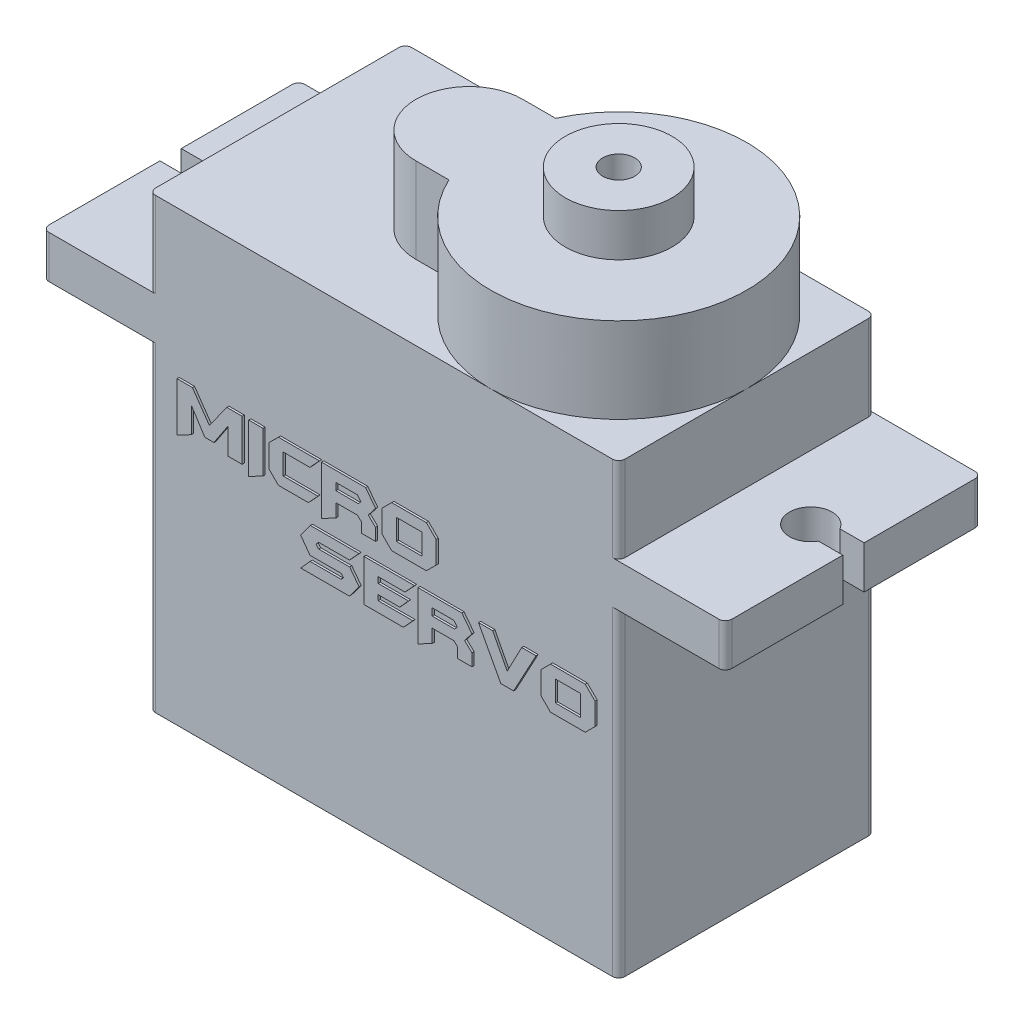
SolidWorks part; units mm, degrees
material "Acrilico TEC"
ref_plane "Front Plane" through (0, 0, 0) normal (0, 0, 1) x (1, 0, 0)
ref_plane "Top Plane" through (0, 0, 0) normal (0, 1, 0) x (1, 0, 0)
ref_plane "Right Plane" through (0, 0, 0) normal (1, 0, 0) x (0, 0, -1)
sketch "Sketch1" plane through (0, 0, 0) normal (0, 1, 0) x (1, 0, 0)
  line L1 (-16, -6) -> (16, -6)
  line L2 (-16, -6) -> (-16, 6)
  line L3 (-16, 6) -> (16, 6)
  line L4 (16, -6) -> (16, 6)
  line L5 (-16, -6) -> (16, 6) construction
  line L6 (-16, 6) -> (16, -6) construction
  point P0 (0, 0)
  dimension "D1" = 32
  dimension "D2" = 12
extrude "Boss-Extrude1" add sketch "Sketch1" along normal blind 2
sketch "Sketch2" plane through (0, 0, 0) normal (0, -1, 0) x (1, 0, 0)
  line L0 (-16, 6) -> (16, 6) construction
  line L1 (-11, -6) -> (11, -6)
  line L2 (-11, -6) -> (-11, 6)
  line L3 (-11, 6) -> (11, 6)
  line L4 (11, -6) -> (11, 6)
  line L5 (-11, -6) -> (11, 6) construction
  line L6 (-11, 6) -> (11, -6) construction
  point P0 (0, 0)
  dimension "D1" = 22
extrude "Boss-Extrude2" add sketch "Sketch2" along normal blind 15
sketch "Sketch3" plane through (0, 2, 0) normal (0, 1, 0) x (1, 0, 0)
  line L0 (16, 6) -> (-16, 6) construction
  line L1 (-11, -6) -> (11, -6)
  line L2 (-11, -6) -> (-11, 6)
  line L3 (-11, 6) -> (11, 6)
  line L4 (11, -6) -> (11, 6)
  line L5 (-11, -6) -> (11, 6) construction
  line L6 (-11, 6) -> (11, -6) construction
  point P0 (0, 0)
  dimension "D1" = 22
extrude "Boss-Extrude3" add sketch "Sketch3" along normal blind 4
sketch "Sketch4" plane through (0, 6, 0) normal (0, 1, 0) x (1, 0, 0)
  line L0 (11, 6) -> (-1, 6)
  line L1 (11, 6) -> (-11, 6) construction
  line L2 (-1, 6) -> (-1, -6)
  line L3 (-11, -6) -> (11, -6) construction
  line L4 (-1, -6) -> (11, 6)
  circle A0 centre (5, 0) radius 6
  dimension "D1" = 12
extrude "Boss-Extrude4" add sketch "Sketch4" along normal blind 4 contours L4 A0 | A0 L4 region at (3.1994, 6, -1.8006) region at (6.8006, 6, 1.8006)
sketch "Sketch5" plane through (0, 6, 0) normal (0, 1, 0) x (1, 0, 0)
  line L0 (5, 0) -> (-2, 0)
  line L1 (-2, 2.5) -> (-0.4544, 2.5)
  line L2 (-2, -2.5) -> (-0.4544, -2.5)
  circle A0 centre (-2, 0) radius 2.5
  circle A1 centre (5, 0) radius 6 construction
  circle A2 centre (5, 0) radius 6
  arc M1 (5, -6) -> (5, 6) centre (5, 0) cw
  dimension "D2" = 5
  dimension "D1" = 7
extrude "Boss-Extrude5" add sketch "Sketch5" along normal blind 4 contours A0 L1 M1 | A0 L2 M1 | A0 M1 region at (-2.4814, 6, 0) region at (-0.901, 6, -2.3763) region at (-0.901, 6, 2.3763)
sketch "Sketch6" plane through (0, 10, 0) normal (0, 1, 0) x (1, 0, 0)
  circle A0 centre (5, 0) radius 2.5
  circle A1 centre (5, 0) radius 0.75
  dimension "D1" = 5
  dimension "D2" = 1.5
extrude "Boss-Extrude6" add sketch "Sketch6" along normal blind 2
sketch "Sketch7" plane through (0, 2, 0) normal (0, 1, 0) x (1, 0, 0)
  line L0 (16, 0) -> (14, 0)
  line L1 (16, -6) -> (16, 6) construction
  line L2 (-16, 0) -> (-14, 0)
  line L3 (-16, 6) -> (-16, -6) construction
  line L5 (18.5, -0.5) -> (13.5, -0.5)
  line L6 (18.5, -0.5) -> (18.5, 0.5)
  line L7 (18.5, 0.5) -> (13.5, 0.5)
  line L8 (13.5, -0.5) -> (13.5, 0.5)
  line L9 (18.5, -0.5) -> (13.5, 0.5) construction
  line L10 (18.5, 0.5) -> (13.5, -0.5) construction
  line L11 (-18.5, -0.5) -> (-13.5, -0.5)
  line L12 (-18.5, -0.5) -> (-18.5, 0.5)
  line L13 (-18.5, 0.5) -> (-13.5, 0.5)
  line L14 (-13.5, -0.5) -> (-13.5, 0.5)
  line L15 (-18.5, -0.5) -> (-13.5, 0.5) construction
  line L16 (-18.5, 0.5) -> (-13.5, -0.5) construction
  circle A0 centre (14, 0) radius 1
  circle A1 centre (-14, 0) radius 1
  dimension "D2" = 2
  dimension "D4" = 2
  dimension "D1" = 2
  dimension "D3" = 2
  dimension "D5" = 1
  dimension "D6" = 5
  dimension "D7" = 1
  dimension "D8" = 5
extrude "Cut-Extrude1" cut sketch "Sketch7" against normal through all contours L7 L8 L5 L6 | A0 | L13 L14 L11 L12 | A1
fillet "Fillet1" radius 0.3 12 edges at (-16, 1, -6) (-16, 1, 6) (16, 1, -6) (16, 1, 6)
sketch "Sketch8" plane through (0, 0, 6) normal (0, 0, 1) x (1, 0, 0)
  text T0 "<b>MICRO</b>" font "BatmanForeverAlternate" height in points 8
  text T1 "<b>SERVO</b>" font "BatmanForeverAlternate" height in points 8
extrude "Boss-Extrude7" add sketch "Sketch8" along normal blind 0.1
